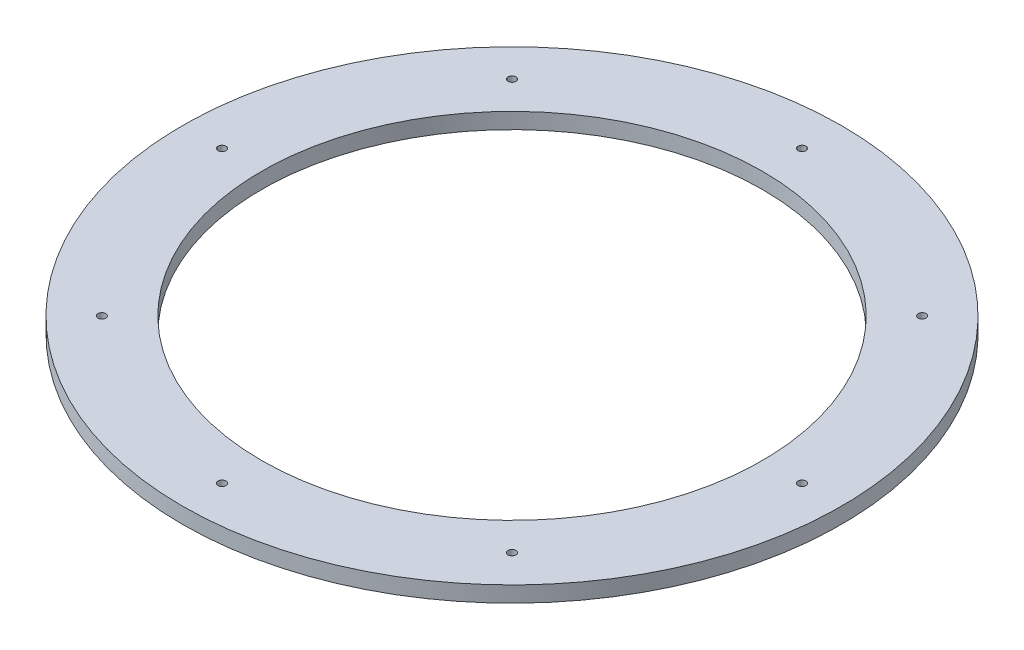
SolidWorks part; units mm, degrees
note: '?' marks a value the reader was unsure of.
ref_plane "Front Plane" through (0, 0, 0) normal (0, 0, 1) x (1, 0, 0)
ref_plane "Top Plane" through (0, 0, 0) normal (0, 1, 0) x (1, 0, 0)
ref_plane "Right Plane" through (0, 0, 0) normal (1, 0, 0) x (0, 0, -1)
sketch "Sketch1" plane through (0, 0, 0) normal (0, 1, 0) x (1, 0, 0)
  line L4 (67.1751, -67.1751) -> (88.3883, -88.3883) construction
  line L5 (95, 0) -> (125, 0) construction
  line L6 (67.1751, 67.1751) -> (88.3883, 88.3883) construction
  line L7 (0, -95) -> (0, -125) construction
  circle A1 centre (0, 0) radius 125
  circle A2 centre (0, -110) radius 1.5
  circle A3 centre (77.7817, -77.7817) radius 1.5
  circle A4 centre (110, 0) radius 1.5
  circle A5 centre (77.7817, 77.7817) radius 1.5
  circle A6 centre (0, 110) radius 1.5
  circle A7 centre (-77.7817, 77.7817) radius 1.5
  circle A8 centre (-110, 0) radius 1.5
  circle A9 centre (-77.7817, -77.7817) radius 1.5
  circle A10 centre (0, 0) radius 95
  point P11 (0, 0)
  point P14 (0, 0)
  dimension "D1" = 15
  dimension "D2" = 15
  dimension "D3" = 15
  dimension "D4" = 15
extrude "Boss-Extrude1" add sketch "Sketch1" along normal blind 6
convert to sheet metal "Convert-Solid1" [suppressed] bend radius? 10 thickness? 4.75
sketch "Bend-Lines1" [suppressed] plane through (0, 0, 0) normal (0, 1, 0) x (1, 0, 0)
sketch "Bounding-Box1" [suppressed] plane through (0, 0, 0) normal (0, 1, 0) x (1, 0, 0)
sheet metal parameters "Sheet-Metal2" thickness 4.75 parameters "D1"=10
flat pattern "Flat-Pattern2" [suppressed]
sketch "Bend-Lines2" plane through (0, 0, 0) normal (0, 1, 0) x (1, 0, 0)
sketch3d "Bounding-Box2" [suppressed]
  line L0 (-125.0764, 124.9235, 0) -> (-124.9234, -125.0764, 0) construction
  line L1 (124.9235, 125.0764, 0) -> (125.0764, -124.9235, 0) construction
  line L2 (-125.0764, 124.9235, 0) -> (124.9235, 125.0764, 0) construction
  line L3 (-124.9234, -125.0764, 0) -> (125.0764, -124.9235, 0) construction
